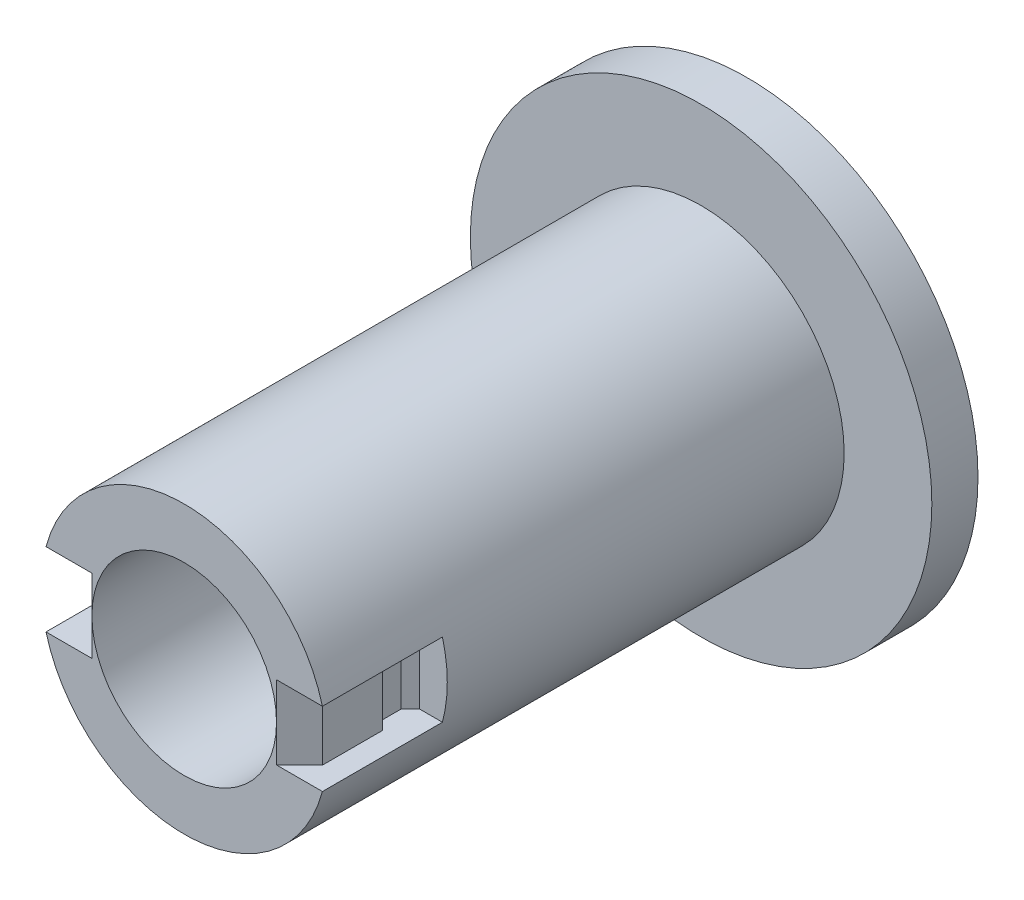
SolidWorks part; units mm, degrees
ref_plane "Front" through (0, 0, 0) normal (0, 0, 1) x (1, 0, 0)
ref_plane "Top" through (0, 0, 0) normal (0, 1, 0) x (1, 0, 0)
ref_plane "Right" through (0, 0, 0) normal (1, 0, 0) x (0, 0, -1)
sketch "Sketch1" plane through (0, 0, 0) normal (0, 0, 1) x (1, 0, 0)
  circle A0 centre (0, 0) radius 15.5
  dimension "D1" = 31
extrude "Boss-Extrude1" add sketch "Sketch1" along normal blind 56
sketch "Sketch4" plane through (0, 0, 0) normal (0, 0, -1) x (-1, 0, 0)
  circle A0 centre (0, 0) radius 25
  dimension "D1" = 50
extrude "Boss-Extrude2" add sketch "Sketch4" along normal blind 5
sketch "Sketch5" plane through (0, 0, 56) normal (0, 0, 1) x (1, 0, 0)
  circle A0 centre (0, 0) radius 10
  dimension "D1" = 20
extrude "Cut-Extrude1" cut sketch "Sketch5" against normal through all
sketch "Sketch6" plane through (0, 0, 0) normal (0, 1, 0) x (1, 0, 0)
  line L0 (10, -56) -> (15.5, -56)
  line L1 (15.5, -56) -> (15.5, -43)
  line L2 (15.5, -56) -> (15.5, 0) construction
  line L3 (15.5, -43) -> (12.5, -43)
  line L5 (11.5, -46) -> (12.5, -47)
  line L6 (12.5, -47) -> (12.5, -53.5)
  line L7 (12.5, -53.5) -> (10, -56)
  line L9 (12.5, -43) -> (11.5, -44)
  line L10 (11.5, -44) -> (11.5, -46)
  dimension "D1" = 1
  dimension "D2" = 5.5
  dimension "D3" = 4
  dimension "D4" = 13
  dimension "D5" = 4
  dimension "D7" = 135
  dimension "D8" = 135
extrude "Cut-Extrude2" cut sketch "Sketch6" against normal blind 4 and the other way blind 4 contours L9 L10 L5 L6 L7 L0 L1 L3 region at (13.7091, 0, 49.5933)
mirror "Mirror1" about plane through (0, 0, 0) normal (1, 0, 0) of "Cut-Extrude2"
